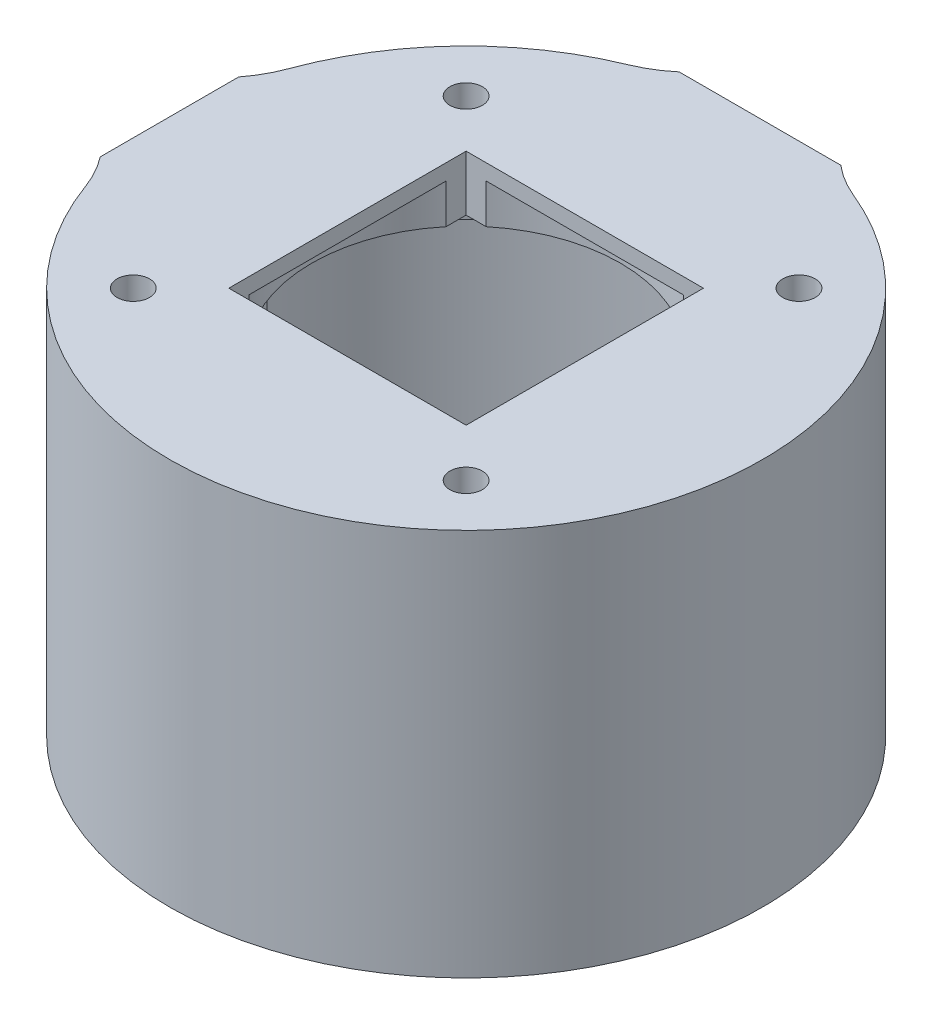
SolidWorks part; units mm, degrees
ref_plane "Спереди" through (0, 0, 0) normal (0, 0, 1) x (1, 0, 0)
ref_plane "Сверху" through (0, 0, 0) normal (0, 1, 0) x (1, 0, 0)
ref_plane "Справа" through (0, 0, 0) normal (1, 0, 0) x (0, 0, -1)
sketch "Sketch1" plane through (0, 0, 0) normal (0, 1, 0) x (1, 0, 0)
  circle A0 centre (0, 0) radius 70
  circle A1 centre (0, 0) radius 75
  dimension "D1" = 140
  dimension "D2" = 150
extrude "Boss-Extrude1" add sketch "Sketch1" along normal blind 78
sketch "Sketch2" plane through (0, 78, 0) normal (0, 1, 0) x (1, 0, 0)
  circle A0 centre (0, 0) radius 75
  circle A1 centre (0, 0) radius 75 construction
extrude "Boss-Extrude2" add sketch "Sketch2" along normal blind 20
sketch "Sketch3" plane through (0, 98, 0) normal (0, 1, 0) x (1, 0, 0)
  line L1 (42.0729, 42.0729) -> (-42.0729, 42.0729) construction
  line L2 (42.0729, 42.0729) -> (42.0729, -42.0729) construction
  line L3 (42.0729, -42.0729) -> (-42.0729, -42.0729) construction
  line L4 (-42.0729, 42.0729) -> (-42.0729, -42.0729) construction
  line L5 (42.0729, 42.0729) -> (-42.0729, -42.0729) construction
  line L6 (42.0729, -42.0729) -> (-42.0729, 42.0729) construction
  line L7 (22.5, 22.5) -> (-22.5, 22.5)
  line L8 (22.5, 22.5) -> (22.5, -22.5)
  line L9 (22.5, -22.5) -> (-22.5, -22.5)
  line L10 (-22.5, 22.5) -> (-22.5, -22.5)
  line L11 (22.5, 22.5) -> (-22.5, -22.5) construction
  line L12 (22.5, -22.5) -> (-22.5, 22.5) construction
  circle A0 centre (0, 0) radius 59.5 construction
  circle A1 centre (-42.0729, -42.0729) radius 4.1
  circle A2 centre (-42.0729, 42.0729) radius 4.1
  circle A3 centre (42.0729, 42.0729) radius 4.1
  circle A4 centre (42.0729, -42.0729) radius 4.1
  dimension "D1" = 119
  dimension "D2" = 8.2
  dimension "D3" = 45
extrude "Cut-Extrude1" cut sketch "Sketch3" against normal through all
sketch "Sketch5" plane through (0, 78, 0) normal (0, -1, 0) x (1, 0, 0)
  line L0 (0, 22.5) -> (0, 70) construction
  line L1 (-22.5, 22.5) -> (22.5, 22.5) construction
  line L3 (-22.5, 45.5) -> (22.5, 45.5)
  line L4 (-22.5, 45.5) -> (-22.5, 22.5)
  line L5 (-22.5, 22.5) -> (22.5, 22.5)
  line L6 (22.5, 45.5) -> (22.5, 22.5)
  line L7 (-22.5, 45.5) -> (22.5, 22.5) construction
  line L8 (-22.5, 22.5) -> (22.5, 45.5) construction
  circle A0 centre (0, 0) radius 70 construction
  point P7 (0, 34)
  dimension "D1" = 23
extrude "Cut-Extrude2" cut sketch "Sketch5" against normal blind 18
sketch "Sketch6" plane through (0, 78, 0) normal (0, -1, 0) x (1, 0, 0)
  circle A0 centre (0, 0) radius 61
  dimension "D1" = 122
extrude "Cut-Extrude3" cut sketch "Sketch6" against normal blind 6
sketch "Sketch7" plane through (0, 84, 0) normal (0, -1, 0) x (1, 0, 0)
  circle A0 centre (-42.0729, -42.0729) radius 10
  circle A1 centre (-42.0729, 42.0729) radius 10
  circle A2 centre (-42.0729, 42.0729) radius 4.1
  circle A3 centre (-42.0729, -42.0729) radius 4.1
  circle A4 centre (42.0729, -42.0729) radius 4.1
  circle A5 centre (42.0729, 42.0729) radius 4.1
  circle A6 centre (42.0729, -42.0729) radius 10
  circle A7 centre (42.0729, 42.0729) radius 10
  dimension "D1" = 20
extrude "Boss-Extrude3" add sketch "Sketch7" along normal up to surface (6 mm away) up to face at (0, 78, 0)
sketch "Sketch8" plane through (0, 84, 0) normal (0, -1, 0) x (1, 0, 0)
  circle A0 centre (0, 0) radius 39
  dimension "D1" = 78
extrude "Cut-Extrude4" cut sketch "Sketch8" against normal blind 10
sketch "Sketch9" plane through (0, 0, 0) normal (0, -1, 0) x (1, 0, 0)
  line L0 (0, -75) -> (0, 75) construction
  line L1 (7.5, -74.6241) -> (-7.5, -74.6241)
  circle A0 centre (0, 0) radius 75 construction
  point P8 (0, -74.6241)
  dimension "D1" = 15
extrude "Cut-Extrude5" cut sketch "Sketch9" against normal through all and the other way through all
sketch "Sketch10" plane through (0, 0, -74.6241) normal (0, 0, -1) x (-1, 0, 0)
  line L0 (0, 0) -> (0, 98) construction
  line L1 (-7.5, 0) -> (7.5, 0) construction
  line L2 (-7.5, 98) -> (7.5, 98) construction
  line L4 (-7.5, 20.4) -> (7.5, 20.4)
  line L5 (-7.5, 20.4) -> (-7.5, 7.6)
  line L6 (-7.5, 7.6) -> (7.5, 7.6)
  line L7 (7.5, 20.4) -> (7.5, 7.6)
  line L8 (-7.5, 20.4) -> (7.5, 7.6) construction
  line L9 (-7.5, 7.6) -> (7.5, 20.4) construction
  point P6 (0, 14)
  dimension "D1" = 12.8
  dimension "D2" = 15
  dimension "D3" = 14
  dimension "D4" = 20.4
extrude "Cut-Extrude6" cut sketch "Sketch10" against normal blind 10
sketch "Sketch11" plane through (0, 0, -74.6241) normal (0, 0, -1) x (-1, 0, 0)
  line L0 (0, 20.4) -> (0, 7.6) construction
  line L1 (7.5, 20.4) -> (-7.5, 20.4) construction
  line L2 (-7.5, 7.6) -> (7.5, 7.6) construction
  line L4 (-10, 4) -> (10, 4)
  line L5 (-10, 4) -> (-10, 24)
  line L6 (-10, 24) -> (10, 24)
  line L7 (10, 4) -> (10, 24)
  line L8 (-10, 4) -> (10, 24) construction
  line L9 (-10, 24) -> (10, 4) construction
  point P6 (0, 14)
  dimension "D1" = 20
  dimension "D2" = 20
extrude "Cut-Extrude7" cut sketch "Sketch11" against normal blind 10 from offset 3 offset against normal yes
sketch "Sketch13" plane through (0, 78, 0) normal (0, -1, 0) x (1, 0, 0)
  line L0 (-70, 0) -> (61, 0) construction
  circle A0 centre (0, 0) radius 70 construction
  arc A1 (-49.6074, 35.4979) -> (-49.6074, -35.4979) centre (0, 0) ccw construction
  circle A2 centre (61, 0) radius 9
  dimension "D1" = 18
extrude "Cut-Extrude9" cut sketch "Sketch13" against normal up to surface (6 mm away) and the other way through all up to face at (0, 84, 20.9638)
sketch "Sketch14" plane through (0, 0, 0) normal (0, -1, 0) x (1, 0, 0)
  line L0 (0, 0) -> (0, -110.0571) construction
  line L2 (10, -94.282) -> (-10, -94.282)
  line L3 (10, -94.282) -> (10, -69.282)
  line L4 (10, -69.282) -> (-10, -69.282) construction
  line L5 (-10, -94.282) -> (-10, -69.282)
  line L6 (10, -94.282) -> (-10, -69.282) construction
  line L7 (10, -69.282) -> (-10, -94.282) construction
  arc A0 (-10, -69.282) -> (10, -69.282) centre (0, 0) ccw construction
  circle A1 centre (0, 0) radius 70 construction
  arc A2 (10, -69.282) -> (-10, -69.282) centre (0, 0) cw
  point P6 (0, -70)
  point P7 (0, -81.782)
  dimension "D1" = 20
  dimension "D2" = 25
  dimension "D3" = 81.782
extrude "Boss-Extrude4" add sketch "Sketch14" against normal up to surface (98 mm away) up to face at (-42.0729, 98, -37.9729)
sketch "Sketch15" plane through (0, 0, 0) normal (0, -1, 0) x (1, 0, 0)
  line L0 (0, -59.1608) -> (0, -94.282) construction
  line L2 (-10, -94.282) -> (10, -94.282) construction
  line L4 (7.55, -91.5916) -> (-7.55, -91.5916)
  line L5 (7.55, -91.5916) -> (7.55, -69.5916)
  line L6 (7.55, -69.5916) -> (-7.55, -69.5916)
  line L7 (-7.55, -91.5916) -> (-7.55, -69.5916)
  line L8 (7.55, -91.5916) -> (-7.55, -69.5916) construction
  line L9 (7.55, -69.5916) -> (-7.55, -91.5916) construction
  circle A0 centre (0, 0) radius 70 construction
  point P6 (0, -80.5916)
  dimension "D1" = 15.1
  dimension "D2" = 22
extrude "Cut-Extrude10" cut sketch "Sketch15" against normal blind 20.4
fillet "Fillet1" radius 30 2 edges at (10, 49, -74.3303) (-10, 49, -74.3303)
sketch "Sketch16" plane through (0, 20.4, 0) normal (0, -1, 0) x (1, 0, 0)
  line L0 (0, -70) -> (0, -91.5916) construction
  line L1 (-7.55, -91.5916) -> (7.55, -91.5916) construction
  line L3 (7.55, -76.1916) -> (-7.55, -76.1916)
  line L4 (7.55, -76.1916) -> (7.55, -91.5916)
  line L5 (7.55, -91.5916) -> (-7.55, -91.5916)
  line L6 (-7.55, -76.1916) -> (-7.55, -91.5916)
  line L7 (7.55, -76.1916) -> (-7.55, -91.5916) construction
  line L8 (7.55, -91.5916) -> (-7.55, -76.1916) construction
  arc A0 (-7.55, -69.5916) -> (7.55, -69.5916) centre (0, 0) ccw construction
  point P7 (0, -83.8916)
  dimension "D1" = 15.4
extrude "Cut-Extrude11" cut sketch "Sketch16" against normal blind 2
sketch "Sketch17" plane through (0, 0, -91.5916) normal (0, 0, 1) x (1, 0, 0)
  line L0 (0, 22.4) -> (0, 0) construction
  line L1 (-7.55, 22.4) -> (7.55, 22.4) construction
  line L2 (-7.55, 0) -> (7.55, 0) construction
  line L4 (7.55, 9.6) -> (-7.55, 9.6)
  line L5 (7.55, 9.6) -> (7.55, 22.4)
  line L6 (7.55, 22.4) -> (-7.55, 22.4)
  line L7 (-7.55, 9.6) -> (-7.55, 22.4)
  line L8 (7.55, 9.6) -> (-7.55, 22.4) construction
  line L9 (7.55, 22.4) -> (-7.55, 9.6) construction
  point P6 (0, 16)
  dimension "D1" = 12.8
  dimension "D2" = 15.1
extrude "Cut-Extrude12" cut sketch "Sketch17" against normal through all
chamfer "Chamfer1" distance 20 angle 74 1 edges at (0, 98, -94.282) first distance on face at (0, 98, -44.4515)
sketch "Sketch19" plane through (0, 20.4, 0) normal (0, -1, 0) x (1, 0, 0)
  line L0 (7.55, -72.2416) -> (-7.55, -72.2416) construction
  line L1 (7.55, -76.1916) -> (7.55, -69.5916) construction
  line L2 (-7.55, -69.5916) -> (-7.55, -76.1916) construction
  line L4 (-7.55, -74.8916) -> (7.55, -74.8916)
  line L5 (-7.55, -74.8916) -> (-7.55, -69.5916)
  line L6 (-7.55, -69.5916) -> (7.55, -69.5916) construction
  line L7 (7.55, -74.8916) -> (7.55, -69.5916)
  line L8 (-7.55, -74.8916) -> (7.55, -69.5916) construction
  line L9 (-7.55, -69.5916) -> (7.55, -74.8916) construction
  arc A4 (-7.55, -69.5916) -> (7.55, -69.5916) centre (0, 0) ccw
  arc A5 (7.55, -69.5916) -> (-7.55, -69.5916) centre (0, 0) ccw construction
  point P6 (0, -72.2416)
  dimension "D1" = 5.3
extrude "Boss-Extrude5" add sketch "Sketch19" along normal blind 5
sketch "Sketch20" plane through (0, 0, 0) normal (0, -1, 0) x (1, 0, 0)
  line L0 (0, 0) -> (-75, 0) construction
  line L2 (-65, -15) -> (-75, -15)
  line L3 (-65, -15) -> (-65, 15)
  line L4 (-65, 15) -> (-75, 15)
  line L5 (-75, -15) -> (-75, 15)
  line L6 (-65, -15) -> (-75, 15) construction
  line L7 (-65, 15) -> (-75, -15) construction
  arc A0 (28.4741, -69.3846) -> (-28.4741, -69.3846) centre (0, 0) ccw construction
  point P7 (-70, 0)
  point P17 (-75, 0)
  dimension "D1" = 10
  dimension "D2" = 30
extrude "Cut-Extrude13" cut sketch "Sketch20" against normal blind 30 from offset 20 offset against normal yes
sketch "Sketch21" plane through (0, 50, 0) normal (0, -1, 0) x (1, 0, 0)
  line L0 (-67.7772, 17.5) -> (-67.7772, -17.5)
  line L3 (-65.8886, 0) -> (-71.3886, 0) construction
  line L4 (-75, -17.5) -> (-67.7772, -17.5)
  line L5 (-75, -17.5) -> (-75, 17.5)
  line L6 (-75, 17.5) -> (-67.7772, 17.5)
  line L8 (-75, -17.5) -> (-67.7772, 17.5) construction
  line L9 (-75, 17.5) -> (-67.7772, -17.5) construction
  arc A1 (-73.4847, 15) -> (-73.4847, -15) centre (0, 0) ccw construction
  circle A3 centre (0, 0) radius 70 construction
  point P3 (-75, 0)
  point P12 (-71.3886, 0)
  dimension "D1" = 35
extrude "Boss-Extrude6" add sketch "Sketch21" along normal up to surface (50 mm away) and the other way up to surface (48 mm away) up to face at (0, 0, -45.6937) other way up to face at (0, 98, -35.5784)
sketch "Sketch22" plane through (-67.7772, 0, 0) normal (1, 0, 0) x (0, 0, -1)
  line L0 (0, 0) -> (0, 78) construction
  line L1 (-17.5, 0) -> (17.5, 0) construction
  line L2 (15, 78) -> (-15, 78)
  line L3 (-15, 78) -> (-15, 48)
  line L4 (17.5, 78) -> (-17.5, 78) construction
  line L5 (-15, 48) -> (15, 48)
  line L6 (15, 48) -> (15, 78)
  line L7 (17.5, 78) -> (-17.5, 78) construction
  point P12 (0, 78)
  dimension "D2" = 30
  dimension "D3" = 30
extrude "Cut-Extrude15" cut sketch "Sketch22" against normal through all
fillet "Fillet2" radius 30 2 edges at (-72.9298, 49, -17.5) (-72.9298, 49, 17.5)
sketch "Sketch23" plane through (0, 98, 0) normal (0, 1, 0) x (1, 0, 0)
  line L1 (-30, 30) -> (30, 30)
  line L2 (-30, 30) -> (-30, -30)
  line L3 (-30, -30) -> (30, -30)
  line L4 (30, 30) -> (30, -30)
  line L5 (-30, 30) -> (30, -30) construction
  line L6 (-30, -30) -> (30, 30) construction
  point P0 (0, 0)
  dimension "D1" = 60
  dimension "D2" = 60
extrude "Cut-Extrude16" cut sketch "Sketch23" against normal through all
sketch "Sketch25" plane through (0, 78, 0) normal (0, -1, 0) x (1, 0, 0)
  line L0 (0, 70) -> (0, -70) construction
  arc A0 (-67.7772, -17.5) -> (70, 0) centre (0, 0) ccw construction
  circle A1 centre (0, 61) radius 6
  arc A2 (35.4979, 49.6074) -> (-35.4979, 49.6074) centre (0, 0) ccw construction
  point P8 (0, 0)
  dimension "D1" = 12
extrude "Cut-Extrude17" cut sketch "Sketch25" against normal up to surface (6 mm away) up to face at (0, 84, 9.1098)
sketch "Sketch26" plane through (0, 78, 0) normal (0, -1, 0) x (1, 0, 0)
  circle A0 centre (-61, 0) radius 11
  arc A1 (-49.6074, 35.4979) -> (-49.6074, -35.4979) centre (0, 0) ccw construction
  dimension "D1" = 22
extrude "Cut-Extrude18" cut sketch "Sketch26" against normal up to surface (6 mm away) up to face at (10.1748, 84, 10.0158)
fillet "Fillet3" radius 6 1 edges at (0, 84, 45.5)
fillet "Fillet4" radius 10 8 edges at (49.6074, 81, 35.4979) (35.4979, 81, 49.6074) (49.6074, 81, -35.4979) (35.4979, 81, -49.6074) (-49.6074, 81, -35.4979) (-35.4979, 81, -49.6074) (-35.4979, 81, 49.6074) (-49.6074, 81, 35.4979)
